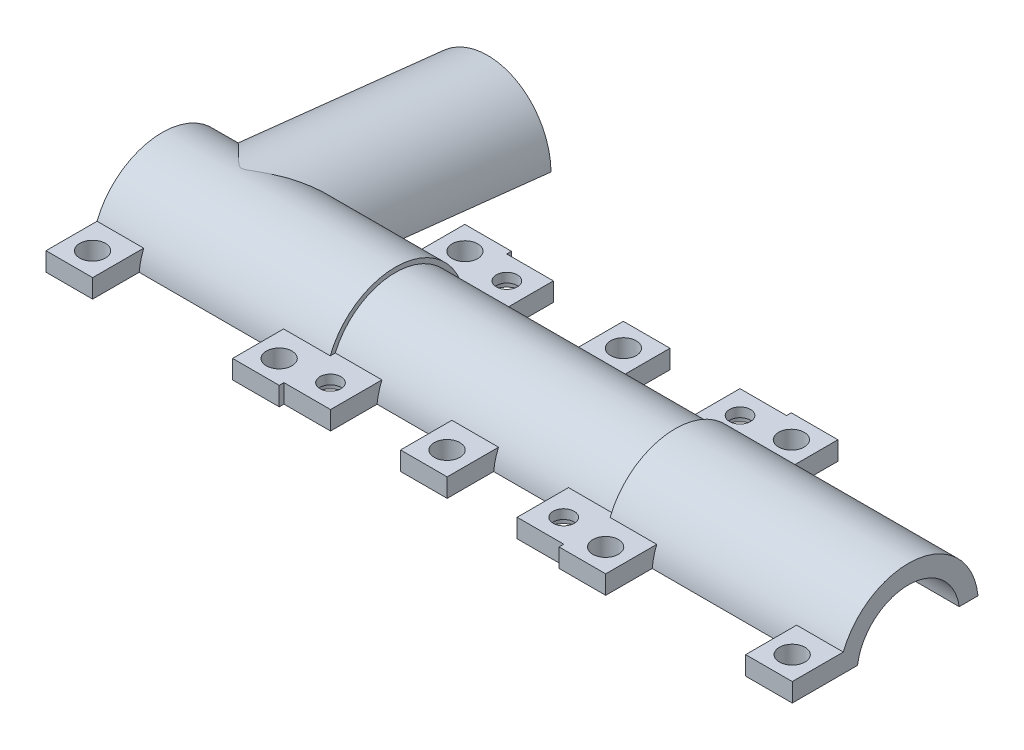
SolidWorks part; units mm, degrees
ref_plane "Front Plane" through (0, 0, 0) normal (0, 0, 1) x (1, 0, 0)
ref_plane "Top Plane" through (0, 0, 0) normal (0, 1, 0) x (1, 0, 0)
ref_plane "Right Plane" through (0, 0, 0) normal (1, 0, 0) x (0, 0, -1)
sketch "Sketch1" plane through (0, 0, 0) normal (1, 0, 0) x (0, 0, -1)
  line L0 (-49.4052, 0) -> (68.181, 0) construction
  line L1 (-13.9194, 1.5) -> (-9.8869, 1.5)
  line L2 (9.8869, 1.5) -> (13.9194, 1.5)
  arc A2 (9.8869, 1.5) -> (-9.8869, 1.5) centre (0, 0) ccw
  arc A3 (-13.9194, 1.5) -> (13.9194, 1.5) centre (0, 0) cw
  dimension "D1" = 1.5
  dimension "D2" = 10
  dimension "D3" = 14
extrude "Boss-Extrude2" add sketch "Sketch1" along normal mid plane 60
sketch "Sketch2" plane through (0, 1.5, 0) normal (0, -1, 0) x (1, 0, 0)
  line L0 (-30, -9.8869) -> (-30, -23.8869)
  line L1 (-30, -23.8869) -> (-20, -23.8869)
  line L2 (-20, -23.8869) -> (-20, -9.8869)
  line L3 (30, -9.8869) -> (-30, -9.8869) construction
  line L4 (-20, -9.8869) -> (-30, -9.8869)
  line L5 (-30, -13.9194) -> (-20, -23.8869) construction
  line L6 (-30, -23.8869) -> (-20, -13.9194) construction
  line L7 (30, -13.9194) -> (-30, -13.9194) construction
  line L8 (0, 27.2864) -> (0, -38.5559) construction
  line L9 (-39.4988, 0) -> (58.103, 0) construction
  line L10 (20, -23.8869) -> (20, -9.8869)
  line L11 (30, -23.8869) -> (20, -23.8869)
  line L12 (30, -9.8869) -> (30, -23.8869)
  line L13 (20, -9.8869) -> (30, -9.8869)
  line L14 (-20, 23.8869) -> (-20, 9.8869)
  line L15 (-30, 23.8869) -> (-20, 23.8869)
  line L16 (-30, 9.8869) -> (-30, 23.8869)
  line L17 (-20, 9.8869) -> (-30, 9.8869)
  line L18 (30, 23.8869) -> (20, 23.8869)
  line L19 (30, 9.8869) -> (30, 23.8869)
  line L20 (20, 9.8869) -> (30, 9.8869)
  line L21 (20, 23.8869) -> (20, 9.8869)
  line L22 (30, 9.8869) -> (-30, 9.8869) construction
  line L23 (-5, 9.8869) -> (5, 9.8869)
  line L24 (-5, 9.8869) -> (-5, 23.8869)
  line L25 (-5, 23.8869) -> (5, 23.8869)
  line L26 (5, 9.8869) -> (5, 23.8869)
  line L27 (-5, -23.8869) -> (5, -23.8869)
  line L28 (5, -9.8869) -> (5, -23.8869)
  line L29 (-5, -9.8869) -> (5, -9.8869)
  line L30 (-5, -9.8869) -> (-5, -23.8869)
  circle A0 centre (-25, -18.9031) radius 2.25
  circle A3 centre (25, 18.9031) radius 2.25
  circle A4 centre (25, -18.9031) radius 2.25
  circle A5 centre (-25, 18.9031) radius 2.25
  circle A6 centre (0, 18.9031) radius 2.75
  circle A7 centre (0, -18.9031) radius 2.75
  dimension "D3" = 5.5
  dimension "D4" = 4.5
  dimension "D1" = 10
  dimension "D2" = 14
extrude "Boss-Extrude3" add sketch "Sketch2" against normal blind 4
sketch "Sketch6" plane through (0, 1.5, 0) normal (0, -1, 0) x (1, 0, 0)
  circle A0 centre (-25, 18.9031) radius 4
  circle A1 centre (25, -18.9031) radius 4
  circle A2 centre (-25, -18.9031) radius 4
  circle A3 centre (25, 18.9031) radius 4
  dimension "D1" = 8
extrude "Cut-Extrude1" cut sketch "Sketch6" against normal blind 2
sketch "Sketch7" plane through (-30, 0, 0) normal (-1, 0, 0) x (0, 0, 1)
  line L0 (-25.7548, 0) -> (29.9478, 0) construction
  line L1 (-9.8869, 1.5) -> (-23.8869, 1.5) construction
  line L2 (23.8869, 1.5) -> (9.8869, 1.5) construction
  line L3 (-14.9248, 1.5) -> (-10.8972, 1.5)
  line L4 (10.8972, 1.5) -> (14.9248, 1.5)
  arc A0 (-10.8972, 1.5) -> (10.8972, 1.5) centre (0, 0) cw
  arc A1 (14.9248, 1.5) -> (-14.9248, 1.5) centre (0, 0) ccw
  dimension "D1" = 11
  dimension "D2" = 15
extrude "Boss-Extrude4" add sketch "Sketch7" along normal blind 50
sketch "Sketch8" plane through (0, 1.5, 0) normal (0, -1, 0) x (1, 0, 0)
  line L0 (-80, 24.8972) -> (-70, 14.9248) construction
  line L5 (-80, 10.8972) -> (-70, 10.8972)
  line L6 (-80, 10.8972) -> (-80, 24.8972)
  line L7 (-80, 24.8972) -> (-70, 24.8972)
  line L8 (-70, 10.8972) -> (-70, 24.8972)
  line L9 (-80, 14.9248) -> (-30, 14.9248) construction
  line L10 (-80, 14.9248) -> (-70, 24.8972) construction
  line L11 (-55, 14.9248) -> (-55, -27.4846) construction
  line L12 (-95.9106, 0) -> (39.2544, 0) construction
  line L13 (-30, 24.8972) -> (-40, 24.8972)
  line L14 (-40, 10.8972) -> (-40, 24.8972)
  line L15 (-30, 10.8972) -> (-40, 10.8972)
  line L16 (-30, 10.8972) -> (-30, 24.8972)
  line L21 (-30, -10.8972) -> (-30, -24.8972)
  line L22 (-30, -10.8972) -> (-40, -10.8972)
  line L23 (-40, -10.8972) -> (-40, -24.8972)
  line L24 (-30, -24.8972) -> (-40, -24.8972)
  circle A0 centre (-75, 19.911) radius 2.75
  circle A1 centre (-35, 19.911) radius 2.75
  circle A3 centre (-35, -19.911) radius 2.75
  dimension "D3" = 5.5
  dimension "D1" = 14
  dimension "D2" = 10
extrude "Boss-Extrude5" add sketch "Sketch8" against normal blind 4
mirror "Mirror1" about plane through (0, 0, 0) normal (1, 0, 0) of "Boss-Extrude4", "Boss-Extrude5"
sketch "Sketch_angle1" plane through (0, 1.5, 0) normal (0, -1, 0) x (1, 0, 0)
  line L0 (0, 0) -> (-80, 0) construction
  line L1 (-80, 10.8972) -> (-80, 24.8972) construction
  line L2 (-65, 0) -> (-58.3309, -190.9781) construction
  line L3 (-65, 0) -> (-65, -122.5894) construction
  point P3 (-45.8937, -154.2934)
  point P9 (-41.5836, -190.9781)
  dimension "D1" = 2
  dimension "D2" = 15
ref_plane "Plane3" through (-64.9208, 0, -2.2671) normal (0.9994, 0, 0.0349) x (0.0349, 0, -0.9994)
sketch "Sketch_angle2" plane through (-64.9208, 0, -2.2671) normal (0.9994, 0, 0.0349) x (0.0349, 0, -0.9994)
  line L0 (0, 0) -> (100, 0) construction
  line L1 (0, 0) -> (50, -3.9351) construction
  point P3 (0, 0)
  point P5 (50, 3.9351)
  dimension "D1" = 4.5
  dimension "D2" = 100
  dimension "D3" = 50
ref_plane "Plane4" through (-63.1759, -3.9351, -52.2366) normal (0.0348, -0.0785, -0.9963) x (-0.9994, 0.0027, -0.0351)
sketch "Sketch13" plane through (-63.1759, -3.9351, -52.2366) normal (0.0348, -0.0785, -0.9963) x (-0.9994, 0.0027, -0.0351)
  line L0 (13.579, 0) -> (-20.9928, 0) construction
  line L1 (10.8972, 1.5) -> (14.7238, 1.5)
  line L2 (-14.7238, 1.5) -> (-10.8972, 1.5)
  arc A0 (10.8972, 1.5) -> (-10.8972, 1.5) centre (0, 0) ccw
  arc A1 (14.7238, 1.5) -> (-14.7238, 1.5) centre (0, 0) ccw
  dimension "D1" = 11
  dimension "D3" = 14.8
  dimension "D2" = 1.5
extrude "Boss-Extrude6" add sketch "Sketch13" against normal up to surface (37.8871 mm away) up to face at (-52, 5.9958, 2.6475)
